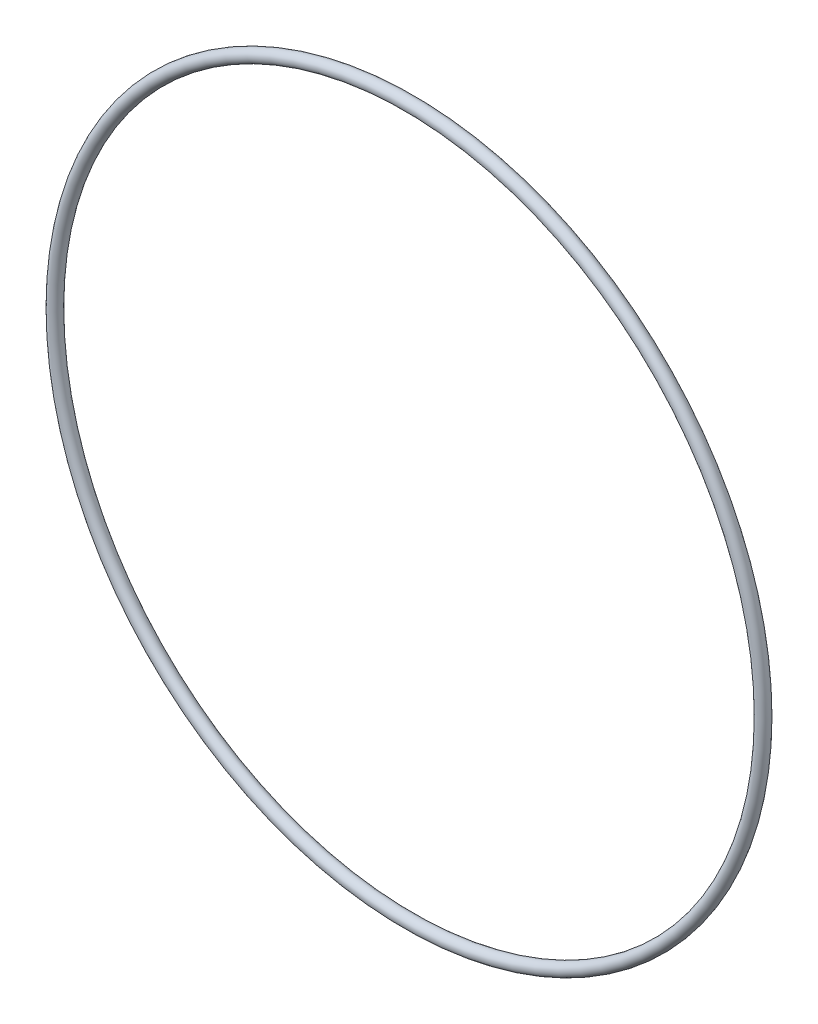
SolidWorks part; units mm, degrees
material "Rubber"
ref_plane "Front Plane" through (0, 0, 0) normal (0, 0, 1) x (1, 0, 0)
ref_plane "Top Plane" through (0, 0, 0) normal (0, 1, 0) x (1, 0, 0)
ref_plane "Right Plane" through (0, 0, 0) normal (1, 0, 0) x (0, 0, -1)
sketch "Sketch1" plane through (0, 0, 0) normal (0, 0, 1) x (1, 0, 0)
  circle A0 centre (0, 0) radius 55
  dimension "D1" = 110
sketch "Sketch2" plane through (0, 0, 0) normal (0, 1, 0) x (1, 0, 0)
  line L0 (-55, 0) -> (55, 0) construction
  circle A0 centre (-50.23, 0) radius 0.89
  dimension "D2" = 1.78
  dimension "D1" = 50.23
sweep "Sweep1" add profiles "Sketch2" path "Sketch1"
